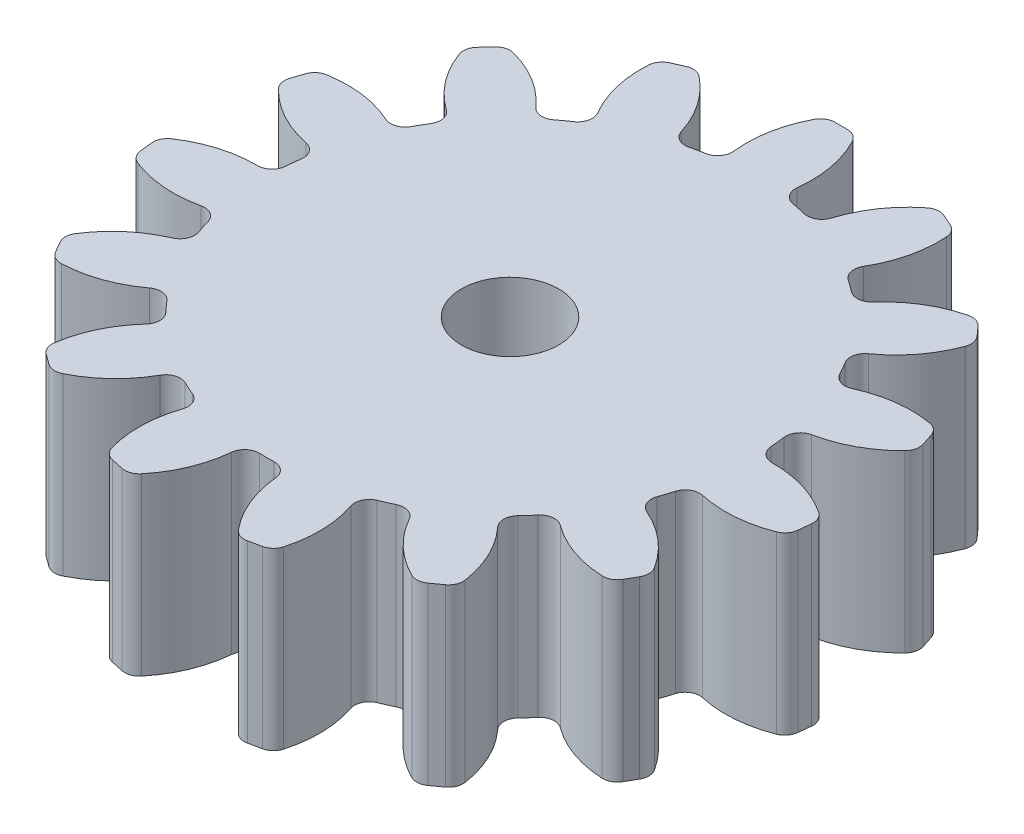
SolidWorks part; units mm, degrees
note: The reader was unsure of these and kept them because the rebuilt part matched: shared geometry of "Sketch1<3>".
ref_plane "Front Plane" through (0, 0, 0) normal (0, 0, 1) x (1, 0, 0)
ref_plane "Top Plane" through (0, 0, 0) normal (0, 1, 0) x (1, 0, 0)
ref_plane "Right Plane" through (0, 0, 0) normal (1, 0, 0) x (0, 0, -1)
sketch "Sketch1" plane through (0, 0, 0) normal (0, 1, 0) x (1, 0, 0)
  line L0 (0, 0) -> (0, 15.1055) construction
  line L1 (0, 17) -> (-0.75, 17)
  line L2 (0, 17) -> (0.75, 17)
  circle A0 centre (0, 0) radius 12.5
  circle A1 centre (0, 0) radius 17 construction
  arc A2 (-0.75, 17) -> (-1.5, 12.4097) centre (4.3336, 13.813) ccw
  arc A3 (0.75, 17) -> (1.5, 12.4097) centre (-4.3336, 13.813) cw
  dimension "D1" = 25
  dimension "D2" = 34
  dimension "D4" = 6
  dimension "D3" = 0.75
  dimension "D5" = 1.5
extrude "Boss-Extrude1" add sketch "Sketch1" along normal blind 9 contours A0
extrude "Boss-Extrude2" add sketch "Sketch1<3>" along normal blind 9 contours A3 L2 L1 A2 A0
sketch "Sketch1<3>" plane through (0, 0, 0) normal (0, 1, 0) x (1, 0, 0) same geometry as "Sketch1"
pattern_circular "CirPattern1" count 15 over 360 about axis through (0, 0, 0) along (0, 1, 0) of "Boss-Extrude2"
sketch "Sketch2" plane through (0, 9, 0) normal (0, 1, 0) x (1, 0, 0)
  circle A0 centre (0, 0) radius 2.5
  dimension "D1" = 5
extrude "Cut-Extrude1" cut sketch "Sketch2" against normal blind 10
fillet "Fillet1" radius 0.75 60 edges at (8.5077, 4.5, 9.158) (9.9971, 4.5, 7.5039) (14.3474, 4.5, 9.1495) (15.0974, 4.5, 7.8505) (11.4971, 4.5, 4.9058) (12.1849, 4.5, 2.7889) (16.8285, 4.5, 2.5229) (16.9853, 4.5, 1.0311) (12.4985, 4.5, -0.1946) (12.2658, 4.5, -2.4082) (16.3997, 4.5, -4.54) (15.9362, 4.5, -5.9666) (11.3388, 4.5, -5.2614) (10.2259, 4.5, -7.189) (13.1353, 4.5, -10.8179) (12.1316, 4.5, -11.9326) (8.2185, 4.5, -9.4184) (6.4178, 4.5, -10.7267) (7.5997, 4.5, -15.2252) (6.2294, 4.5, -15.8353) (3.6772, 4.5, -11.9469) (-3.6772, 4.5, -11.9469) (-6.2294, 4.5, -15.8353) (-7.5997, 4.5, -15.2252) (-6.4178, 4.5, -10.7267) (-8.2185, 4.5, -9.4184) (-12.1316, 4.5, -11.9326) (-13.1353, 4.5, -10.8179) (-10.2259, 4.5, -7.189) (-11.3388, 4.5, -5.2614) (-15.9362, 4.5, -5.9666) (-16.3997, 4.5, -4.54) (-12.2658, 4.5, -2.4082) (-12.4985, 4.5, -0.1946) (-16.9853, 4.5, 1.0311) (-16.8285, 4.5, 2.5229) (-12.1849, 4.5, 2.7889) (-11.4971, 4.5, 4.9058) (-15.0974, 4.5, 7.8505) (-14.3474, 4.5, 9.1495) (-9.9971, 4.5, 7.5039) (-8.5077, 4.5, 9.158) (-10.5991, 4.5, 13.3124) (-9.3856, 4.5, 14.1941) (-6.0807, 4.5, 10.9213) (1.5, 4.5, -12.4097) (-4.0473, 4.5, 11.8266) (-4.2681, 4.5, 16.4726) (-2.8009, 4.5, 16.7844) (-1.1129, 4.5, 12.4504) (0.75, 4.5, -17) (1.1129, 4.5, 12.4504) (2.8009, 4.5, 16.7844) (4.2681, 4.5, 16.4726) (4.0473, 4.5, 11.8266) (-0.75, 4.5, -17) (-1.5, 4.5, -12.4097) (6.0807, 4.5, 10.9213) (9.3856, 4.5, 14.1941) (10.5991, 4.5, 13.3124)
